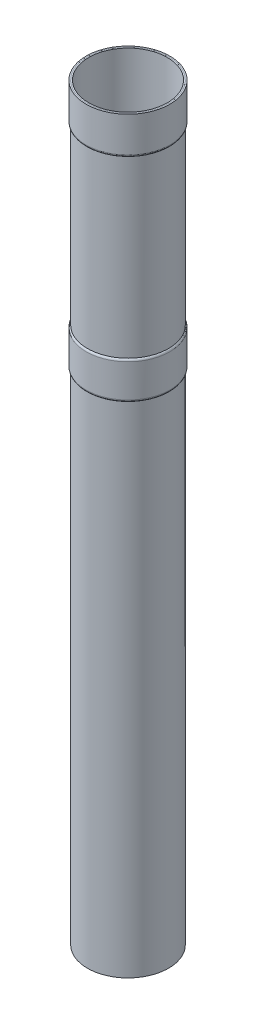
SolidWorks part; units mm, degrees
material "Plástico personalizado"
ref_plane "Plano frontal" through (0, 0, 0) normal (0, 0, 1) x (1, 0, 0)
ref_plane "Plano superior" through (0, 0, 0) normal (0, 1, 0) x (1, 0, 0)
ref_plane "Plano direito" through (0, 0, 0) normal (1, 0, 0) x (0, 0, -1)
sketch "Esboço1" plane through (0, 0, 0) normal (0, 1, 0) x (1, 0, 0)
  circle A0 centre (0, 0) radius 32.5
  circle A1 centre (0, 0) radius 31.5
extrude "Ressalto-extrusão1" add sketch "Esboço1" along normal blind 600 contours A0 | A1
sketch "Esboço2" plane through (0, 600, 0) normal (0, 1, 0) x (1, 0, 0)
  circle A1 centre (0, 0) radius 32.5
  circle A2 centre (0, 0) radius 33.5
extrude "Ressalto-extrusão2" add sketch "Esboço2" against normal blind 30 separate body
sketch "Esboço4" plane through (0, 0, 0) normal (0, -1, 0) x (1, 0, 0)
  circle A0 centre (0, 0) radius 32.5
  circle A1 centre (0, 0) radius 33.5
extrude "Ressalto-extrusão3" add sketch "Esboço4" against normal blind 430
sketch "Esboço5" plane through (0, 0, 0) normal (0, -1, 0) x (1, 0, 0)
  circle A0 centre (0, 0) radius 32.5
  circle A1 centre (0, 0) radius 33.5
extrude "Corte-extrusão1" cut sketch "Esboço5" against normal blind 400
fillet "Filete4" radius 2 1 edges at (0, 400, -33.5)
fillet "Filete8" radius 2 1 edges at (0, 430, -33.5)
fillet "Filete9" radius 2 1 edges at (0, 570, 33.5)
